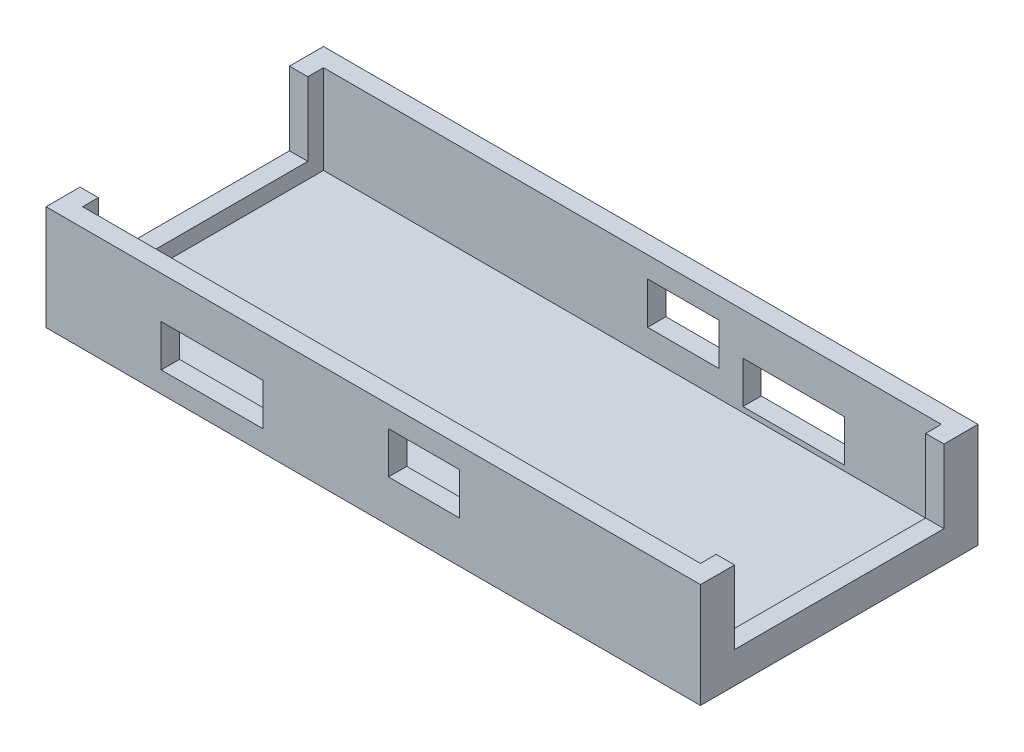
SolidWorks part; units mm, degrees
ref_plane "Front Plane" through (0, 0, 0) normal (0, 0, 1) x (1, 0, 0)
ref_plane "Top Plane" through (0, 0, 0) normal (0, 1, 0) x (1, 0, 0)
ref_plane "Right Plane" through (0, 0, 0) normal (1, 0, 0) x (0, 0, -1)
sketch "Croquis1" plane through (0, 0, 0) normal (0, 1, 0) x (1, 0, 0)
  line L1 (31.25, 13.25) -> (-31.25, 13.25)
  line L2 (31.25, 13.25) -> (31.25, -13.25)
  line L3 (31.25, -13.25) -> (-31.25, -13.25)
  line L4 (-31.25, 13.25) -> (-31.25, -13.25)
  line L5 (31.25, 13.25) -> (-31.25, -13.25) construction
  line L6 (31.25, -13.25) -> (-31.25, 13.25) construction
  point P0 (0, 0)
  dimension "D1" = 62.5
  dimension "D2" = 26.5
extrude "Saliente-Extruir1" add sketch "Croquis1" along normal blind 10
sketch "Croquis2" plane through (0, 0, 0) normal (0, 1, 0) x (1, 0, 0)
  line L1 (29.5, 11.5) -> (-29.5, 11.5)
  line L2 (29.5, 11.5) -> (29.5, -11.5)
  line L3 (29.5, -11.5) -> (-29.5, -11.5)
  line L4 (-29.5, 11.5) -> (-29.5, -11.5)
  line L5 (29.5, 11.5) -> (-29.5, -11.5) construction
  line L6 (29.5, -11.5) -> (-29.5, 11.5) construction
  point P0 (0, 0)
  dimension "D1" = 59
  dimension "D2" = 23
extrude "Cortar-Extruir1" cut sketch "Croquis2" against normal blind 8.5 from surface starting at face at (0, 10, 0)
sketch "Croquis3" plane through (0, 0, 13.25) normal (0, 0, 1) x (1, 0, 0)
sketch "Croquis4" plane through (0, 0, 0) normal (1, 0, 0) x (0, 0, -1)
  line L0 (-13.25, 0) -> (13.25, 0) construction
  line L1 (-13.25, 10) -> (-13.25, 0) construction
  line L13 (-10, 10) -> (-10, 3)
  line L14 (10, 10) -> (-10, 10)
  line L15 (-10, 3) -> (10, 3)
  line L16 (10, 3) -> (10, 10)
  dimension "D1" = 20
  dimension "D2" = 3
  dimension "D3" = 3.25
  dimension "D4" = 7
sketch "Croquis6" plane through (0, 0, 0) normal (0, 0, 1) x (1, 0, 0)
  line L0 (31.25, 10) -> (31.25, 0) construction
  line L2 (4.7531, 4) -> (4.7531, 0) construction
  line L3 (-31.25, 0) -> (31.25, 0) construction
  line L4 (4.7531, 10) -> (4.7531, 8) construction
  line L5 (-31.25, 10) -> (31.25, 10) construction
  line L6 (8.25, 4) -> (1.45, 4)
  line L7 (1.45, 8) -> (8.25, 8)
  line L8 (8.25, 8) -> (8.25, 4)
  line L9 (1.45, 8) -> (1.45, 4)
  dimension "D1" = 4
  dimension "D2" = 4
  dimension "D3" = 23
  dimension "D4" = 6.8
extrude "Cortar-Extruir4" cut sketch "Croquis6" against normal blind 40 from surface starting at face at (0, 5, 13.25)
sketch "Croquis7" plane through (0, 0, 0) normal (0, 0, 1) x (1, 0, 0)
  line L0 (-31.25, 5) -> (-20.25, 5) construction
  line L1 (-31.25, 10) -> (-31.25, 0) construction
  line L2 (-20.25, 10) -> (-20.25, 6) construction
  line L3 (-31.25, 10) -> (31.25, 10) construction
  line L4 (-20.25, 6) -> (-10.55, 6)
  line L5 (-10.55, 6) -> (-10.55, 2)
  line L6 (-10.55, 2) -> (-20.25, 2)
  line L7 (-20.25, 2) -> (-20.25, 6)
  dimension "D1" = 11
  dimension "D2" = 4
  dimension "D3" = 9.7
  dimension "D4" = 4
extrude "Cortar-Extruir5" cut sketch "Croquis7" against normal blind 11 from surface starting at face at (4.85, 6, 13.25)
sketch "Croquis10" plane through (0, 0, -13.25) normal (0, 0, -1) x (-1, 0, 0)
  line L0 (-31.25, 6) -> (-20.25, 6) construction
  line L1 (-31.25, 10) -> (-31.25, 0) construction
  line L2 (-31.25, 10) -> (31.25, 10) construction
  line L3 (-20.25, 6) -> (-10.55, 6)
  line L4 (-10.55, 2) -> (-20.25, 2)
  line L5 (-20.25, 2) -> (-20.25, 6)
  line L6 (-10.55, 6) -> (-10.55, 2)
  dimension "D1" = 11
  dimension "D2" = 4
  dimension "D3" = 9.7
  dimension "D4" = 4
extrude "Cortar-Extruir6" cut sketch "Croquis10" against normal blind 11
sketch "Croquis11" plane through (0, 0, 0) normal (0, -1, 0) x (-1, 0, 0)
  line L0 (-7.25, -5.5) -> (-21.25, -5.5)
  line L1 (31.25, 13.25) -> (31.25, -13.25) construction
  line L2 (0, -12.0381) -> (0, 10.1717) construction
  line L3 (-21.25, 5.5) -> (-21.25, -5.5)
  line L4 (-7.25, 5.5) -> (-21.25, 5.5)
  line L5 (7.25, 5.5) -> (21.25, 5.5)
  line L6 (7.25, 5.5) -> (7.25, -5.5)
  line L7 (7.25, -5.5) -> (21.25, -5.5)
  line L8 (21.25, 5.5) -> (21.25, -5.5)
  line L9 (7.25, 5.5) -> (21.25, -5.5) construction
  line L10 (7.25, -5.5) -> (21.25, 5.5) construction
  line L11 (-7.25, 5.5) -> (-7.25, -5.5)
  point P9 (14.25, 0)
  dimension "D1" = 14
  dimension "D2" = 10
  dimension "D3" = 11
extrude "Saliente-Extruir2" add sketch "Croquis11" along normal blind 2
sketch "Croquis12" plane through (0, 0, -5.5) normal (0, 0, -1) x (-1, 0, 0)
  line L0 (21.25, 0) -> (7.25, 0) construction
  line L1 (9.25, 0) -> (19.25, 0)
  line L2 (9.25, 0) -> (9.25, -1.25)
  line L3 (9.25, -1.25) -> (19.25, -1.25)
  line L4 (19.25, 0) -> (19.25, -1.25)
  line L5 (9.25, 0) -> (19.25, -1.25) construction
  line L6 (9.25, -1.25) -> (19.25, 0) construction
  line L8 (7.25, -2) -> (7.25, 0) construction
  line L9 (0, 3.9175) -> (0, -4.429) construction
  line L10 (-9.25, -1.25) -> (-19.25, -1.25)
  line L11 (-19.25, 0) -> (-19.25, -1.25)
  line L12 (-9.25, 0) -> (-19.25, 0)
  line L13 (-9.25, 0) -> (-9.25, -1.25)
  point P0 (14.25, -0.625)
  dimension "D1" = 1.25
  dimension "D2" = 0
  dimension "D3" = 10
  dimension "D4" = 2
extrude "Cortar-Extruir7" cut sketch "Croquis12" against normal blind 22
fillet "Redondeo1" radius 0.5 44 edges at (-9.25, 0, 0) (-7.25, 0, 0) (-19.25, 0, 0) (19.25, 0, 0) (21.25, 0, 0) (7.25, 0, 0) (9.25, 0, 0) (7.25, -1, -5.5) (21.25, -1, -5.5) (20.25, 0, -5.5) (19.25, -0.625, -5.5) (14.25, -1.25, -5.5) (9.25, -0.625, -5.5) (8.25, 0, -5.5) (-21.25, 0, 0) (-21.25, -1, -5.5) (-7.25, -1, -5.5) (-8.25, 0, -5.5) (-9.25, -0.625, -5.5) (-14.25, -1.25, -5.5) (-19.25, -0.625, -5.5) (-20.25, 0, -5.5) (-9.25, -0.625, 5.5) (-8.25, 0, 5.5) (-7.25, -1, 5.5) (-21.25, -1, 5.5) (-20.25, 0, 5.5) (-19.25, -0.625, 5.5) (-14.25, -1.25, 5.5) (-14.25, -2, 5.5) (-7.25, -2, 0) (-14.25, -2, -5.5) (-21.25, -2, 0) (21.25, -2, 0) (14.25, -2, -5.5) (7.25, -2, 0) (19.25, -0.625, 5.5) (20.25, 0, 5.5) (21.25, -1, 5.5) (14.25, -2, 5.5) (7.25, -1, 5.5) (8.25, 0, 5.5) (9.25, -0.625, 5.5) (14.25, -1.25, 5.5)
extrude "Cortar-Extruir8" cut sketch "Croquis4" against normal blind 10 from surface starting at face at (31.25, 5, 0)
extrude "Cortar-Extruir9" cut sketch "Croquis4<3>" along normal blind 10 from surface starting at face at (-31.25, 5, 0)
sketch "Croquis4<3>" plane through (0, 0, 0) normal (1, 0, 0) x (0, 0, -1) same geometry as "Croquis4"
